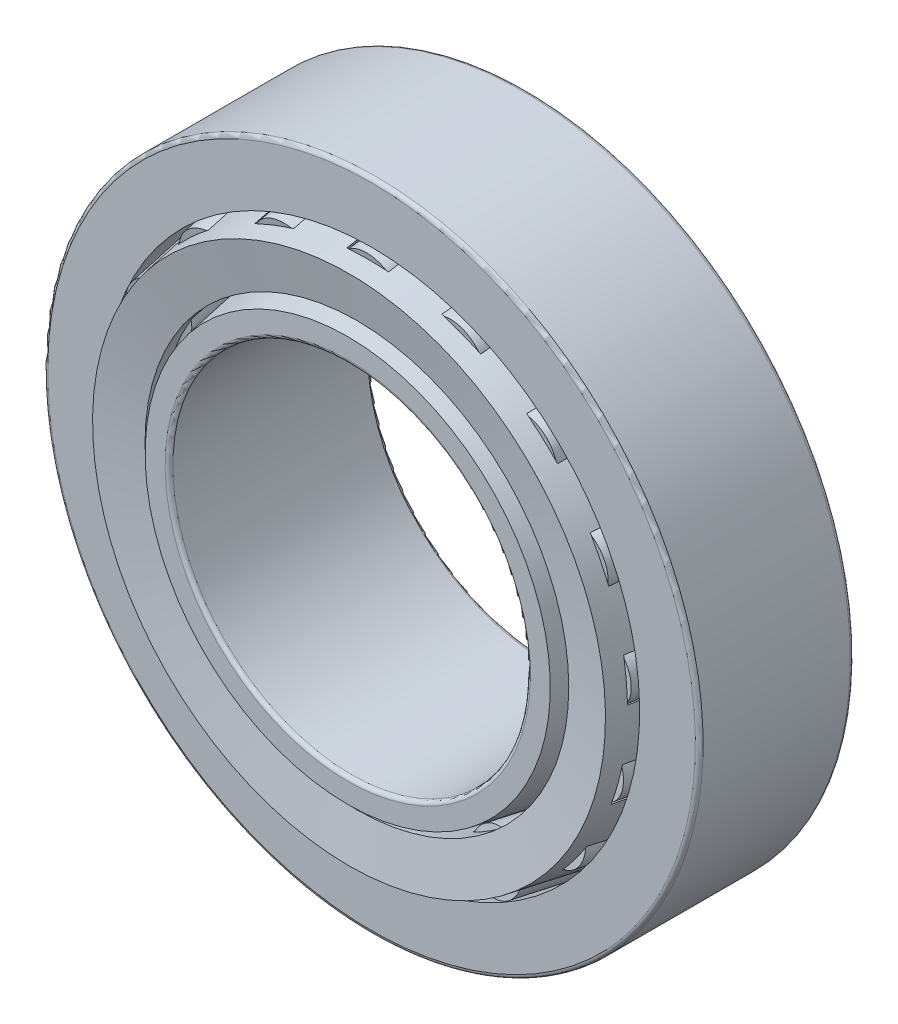
SolidWorks part; units mm, degrees
ref_plane "Front Plane" through (0, 0, 0) normal (0, 0, 1) x (1, 0, 0)
ref_plane "Top Plane" through (0, 0, 0) normal (0, 1, 0) x (1, 0, 0)
ref_plane "Right Plane" through (0, 0, 0) normal (1, 0, 0) x (0, 0, -1)
sketch "Sketch1" plane through (0, 0, 0) normal (1, 0, 0) x (0, 0, -1)
  line L0 (-8.5, 0) -> (8.5, 0) construction
  line L1 (0, 0) -> (0, 27.5) construction
  line L2 (-8.5, 15) -> (8.5, 15) construction
  line L3 (8.5, 15) -> (8.5, 20) construction
  line L4 (8.5, 20) -> (-8.5, 17.0024) construction
  line L5 (-8.5, 17.0024) -> (-8.5, 15) construction
  line L7 (-6.5, 27.5) -> (6.5, 27.5)
  line L8 (6.5, 27.5) -> (6.5, 24.7923)
  line L9 (6.5, 24.7923) -> (-6.5, 22.5)
  line L10 (-6.5, 22.5) -> (-6.5, 27.5)
  line L12 (8.0202, 25.0603) -> (8.9, 20.0705) construction
  line L13 (-7.6202, 17.1576) -> (-8.5, 22.1473) construction
  line L14 (-8.5, 17.0024) -> (-7.6202, 17.1576) construction
  line L15 (-8.5, 17.0024) -> (8.9, 20.0705) construction
  line L20 (-8.5, -17.0024) -> (8.9, -20.0705) construction
  line L21 (-8.5, -17.0024) -> (-7.6202, -17.1576) construction
  line L22 (-7.6202, -17.1576) -> (-8.5, -22.1473) construction
  line L23 (8.0202, -25.0603) -> (8.9, -20.0705) construction
  line L24 (-8.5, -17.0024) -> (-8.5, -15) construction
  line L25 (8.5, -20) -> (-8.5, -17.0024) construction
  line L26 (8.5, -15) -> (8.5, -20) construction
  line L27 (-8.5, -15) -> (8.5, -15) construction
  line L28 (-6.5, -22.5) -> (-6.5, -27.5) construction
  line L29 (6.5, -24.7923) -> (-6.5, -22.5) construction
  line L30 (6.5, -27.5) -> (6.5, -24.7923) construction
  line L31 (-6.5, -27.5) -> (6.5, -27.5) construction
  point P5 (0, 15)
  point P37 (0, -15)
  dimension "OD" = 55
  dimension "Shaft Dia" = 30
  dimension "D1" = 100
  dimension "D2" = 12.5
  dimension "D3" = 5
revolve "Revolve1" add sketch "Sketch1" angle 360 about L0
sketch "Sketch5" plane through (0, 0, 0) normal (1, 0, 0) x (0, 0, -1)
  line L0 (8.5, 20) -> (-8.5, 17.0024) construction
  line L1 (8.5, 20) -> (-8.5, 17.0024)
  line L2 (-8.5, 17.0024) -> (-8.5, 15)
  line L3 (-8.5, 15) -> (8.5, 15)
  line L4 (8.5, 15) -> (8.5, 20)
revolve "Revolve4" add sketch "Sketch5" angle 360 about L0
sketch "Sketch2" plane through (0, 0, 0) normal (1, 0, 0) x (0, 0, -1)
  line L0 (-8.39, 21.5236) -> (-7.7301, 17.7813)
  line L1 (6.5, 24.1491) -> (8.1301, 24.4366)
  line L2 (-7.7301, 17.7813) -> (6.5, 20.2905)
  line L3 (8.0202, 25.0603) -> (8.9, 20.0705) construction
  line L4 (6.5, 20.2905) -> (6.5, 24.1491) construction
  line L5 (6.5, 24.1491) -> (-8.39, 21.5236)
  line L6 (6.5, 24.7923) -> (-6.5, 22.5) construction
  line L7 (8.5, 20) -> (-8.5, 17.0024) construction
  line L8 (-8.5, 22.1473) -> (6.5, 24.7923) construction
  line L9 (-7.6202, 17.1576) -> (8.9, 20.0705) construction
  line L10 (8.1301, 24.4366) -> (8.79, 20.6943)
  line L11 (-8.5, 22.1473) -> (-8.39, 21.5236) construction
  line L12 (6.5, -27.5) -> (6.5, 27.5) construction
  line L13 (6.5, 27.5) -> (6.5, 24.7923) construction
  line L14 (8.79, 20.6943) -> (6.5, 20.2905)
  line L15 (-7.7301, 17.7813) -> (-7.6202, 17.1576) construction
  line L16 (0, 0) -> (-8.5, 0) construction
  line L17 (-8.5, 17.0024) -> (-8.5, -17.0024) construction
  line L18 (-7.7301, -17.7813) -> (-7.6202, -17.1576) construction
  line L19 (-8.5, -22.1473) -> (-8.39, -21.5236) construction
  line L20 (-7.6202, -17.1576) -> (8.9, -20.0705) construction
  line L21 (-8.5, -22.1473) -> (6.5, -24.7923) construction
  line L22 (6.5, -20.2905) -> (6.5, -24.1491) construction
  line L23 (8.79, -20.6943) -> (6.5, -20.2905) construction
  line L24 (8.1301, -24.4366) -> (8.79, -20.6943) construction
  line L25 (6.5, -24.1491) -> (-8.39, -21.5236) construction
  line L26 (-7.7301, -17.7813) -> (6.5, -20.2905) construction
  line L27 (6.5, -24.1491) -> (8.1301, -24.4366) construction
  line L28 (-8.39, -21.5236) -> (-7.7301, -17.7813) construction
  dimension "D2" = 3.8001
  dimension "D1" = 5.0667
revolve "Revolve2" add sketch "Sketch2" angle 360 about L0
sketch "Sketch3" plane through (0, 0, 0) normal (1, 0, 0) x (0, 0, -1)
  line L0 (-8.0601, 19.6525) -> (6.5, 22.2198) construction
  line L1 (-8.39, 21.5236) -> (-7.7301, 17.7813) construction
  line L2 (6.5, 20.2905) -> (6.5, 24.1491) construction
  line L3 (-6.5, 19.9275) -> (-6.9399, 22.4224)
  line L5 (-6.9399, 22.4224) -> (6.0601, 24.7147)
  line L6 (6.0601, 24.7147) -> (6.5, 22.2198)
  line L7 (6.5, 22.2198) -> (-6.5, 19.9275)
  line L11 (-8.0601, 19.6525) -> (-6.5, 19.9275) construction
  line L12 (-6.5, 27.5) -> (-6.5, -27.5) construction
  line L13 (-8.0601, 19.6525) -> (-6.5, 19.9275) construction
revolve "Cut-Revolve1" cut sketch "Sketch3" angle 360 about L0
sketch "Sketch4" plane through (0, 0, 0) normal (1, 0, 0) x (0, 0, -1)
  line L0 (-6.9179, 22.2974) -> (6.0821, 24.5896)
  line L1 (6.0821, 24.5896) -> (6.5, 22.2198)
  line L2 (6.5, 22.2198) -> (-6.5, 19.9275)
  line L3 (-6.5, 19.9275) -> (-8.0601, 19.6525) construction
  line L4 (-6.5, 19.9275) -> (-6.9179, 22.2974)
  line L5 (-8.0601, 19.6525) -> (-6.5, 19.9275) construction
  line L6 (6.5, 22.2198) -> (-6.5, 19.9275) construction
  line L7 (6.5, 24.7923) -> (-6.5, 22.5) construction
  line L8 (0, 0) -> (-8.5, 0) construction
  line L9 (-8.5, 0) -> (8.5, 0) construction
  line L10 (-8.0601, -19.6525) -> (-6.5, -19.9275) construction
  line L11 (-6.5, -19.9275) -> (-8.0601, -19.6525) construction
  line L12 (-6.5, -19.9275) -> (-6.9179, -22.2974) construction
  line L13 (6.5, -22.2198) -> (-6.5, -19.9275) construction
  line L14 (6.0821, -24.5896) -> (6.5, -22.2198) construction
  line L15 (-6.9179, -22.2974) -> (6.0821, -24.5896) construction
  dimension "D1" = 0.127
revolve "Revolve3" add sketch "Sketch4" angle 360 about L0
sketch "Sketch7" plane through (0, 0, 0) normal (0, 0, 1) x (1, 0, 0)
  line L0 (0, 0) -> (-2.8864, 23.7334) construction
  line L1 (0, 0) -> (2.8864, 23.7334) construction
  ellipse E0 centre (0, 19.9275) end of major axis (-2.4064, 19.9275) minor radius 2.3698 construction
  dimension "D1" = 13.868
ref_axis "Axis1" through (0, 0, -8.5) along (0, 0, 1)
pattern_circular "CirPattern2" count 17 over 360 about axis through (0, 0, -8.5) along (0, 0, 1) of bodies 403
pattern_circular "CirPattern1" count 17 over 360 about axis through (0, 0, -8.5) along (0, 0, 1) of "Cut-Revolve1"
fillet "Fillet1" radius 0.325 2 edges at (0, -27.5, -6.5) (0, -27.5, 6.5)
fillet "Fillet2" radius 0.325 2 edges at (0, -15, -8.5) (0, -15, 8.5)
sketch "Sketch6" plane through (0, 0, 0) normal (1, 0, 0) x (0, 0, -1)
  line L0 (-46.39, 27.5) -> (-46.39, 22.5)
  line L1 (-46.39, 22.5) -> (-33.39, 24.7923)
  line L2 (-33.39, 24.7923) -> (-33.39, 27.5)
  line L3 (-33.39, 27.5) -> (-46.39, 27.5)
  line L4 (-6.5, 27.5) -> (6.5, 27.5) construction
  line L5 (6.5, 27.5) -> (6.5, 24.7923) construction
  line L6 (6.5, 24.7923) -> (-6.5, 22.5) construction
  line L7 (-8.39, -21.5236) -> (-8.39, 21.5236) construction
  dimension "D1" = 25
revolve "Revolve5" [suppressed] add sketch "Sketch6" angle 360 about L0
fillet "Fillet3" [suppressed] radius 0.325
delete or keep bodies "Body-Delete1" [suppressed] type delete bodies bodies 399
equation "\"D3@Sketch1\" = \"D2@Sketch1\"/2.5"
equation "\"D2@Sketch2\" = \"D1@Sketch2\"*.75"
equation "\"D1@Fillet1\"= \"Width@Sketch1\" * .025"
equation "\"D1@Fillet2\" = \"D1@Fillet1\""
equation "\"D1@Fillet3\" = \"D1@Fillet1\""
equation "\"Rollers@CirPattern2\"=(360/\"D1@Sketch7\")/1.50"
equation "\"D1@CirPattern1\"=\"Rollers@CirPattern2\""
